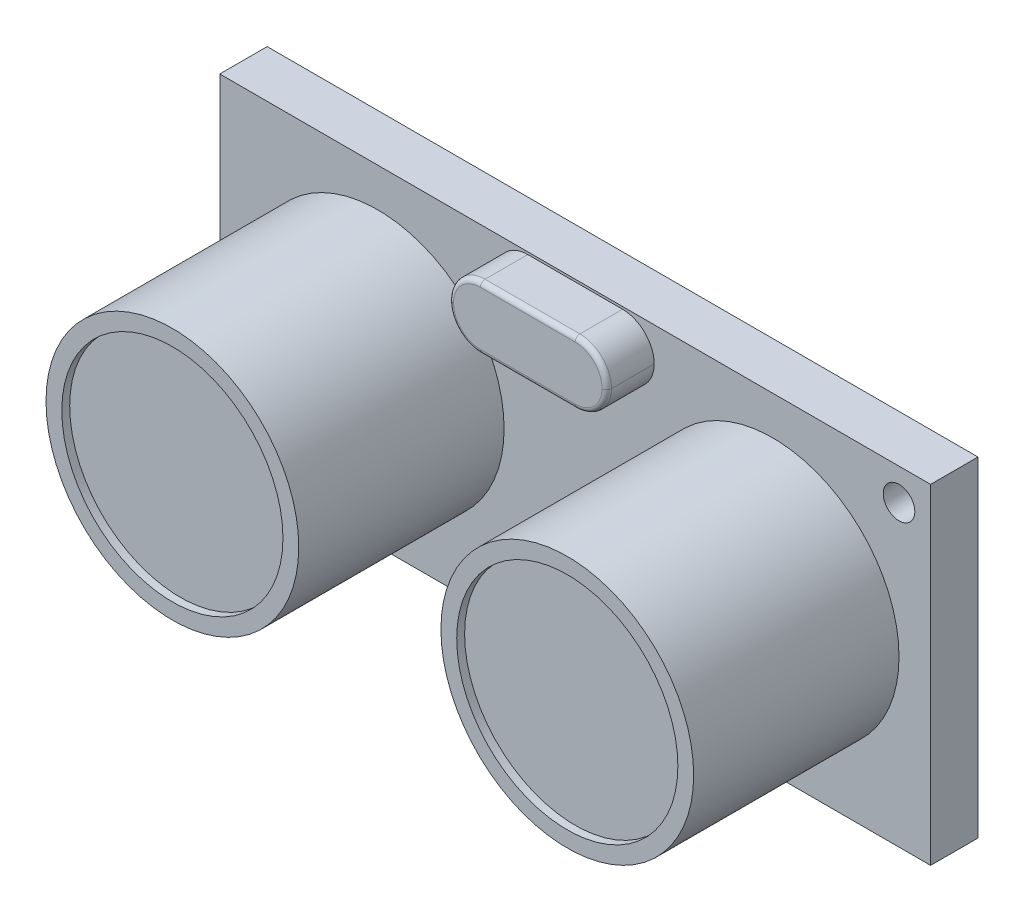
SolidWorks part; units mm, degrees
ref_plane "Front Plane" through (0, 0, 0) normal (0, 0, 1) x (1, 0, 0)
ref_plane "Top Plane" through (0, 0, 0) normal (0, 1, 0) x (1, 0, 0)
ref_plane "Right Plane" through (0, 0, 0) normal (1, 0, 0) x (0, 0, -1)
sketch "Sketch1" plane through (0, 0, 0) normal (0, 0, 1) x (1, 0, 0)
  line L0 (-22.5, 10.445) -> (22.5, 10.445)
  line L1 (-22.5, 10.445) -> (-22.5, -10.445)
  line L2 (-22.5, -10.445) -> (22.5, -10.445)
  line L3 (22.5, 10.445) -> (22.5, -10.445)
  line L4 (0, 10.445) -> (0, -10.445) construction
  line L5 (-22.5, 0) -> (22.5, 0) construction
  circle A2 centre (-20.5, -8.445) radius 1
  circle A3 centre (20.5, 8.445) radius 1
  point P16 (0, 0)
  point P26 (-22.5, 0)
  point P30 (22.5, 0)
  dimension "D16" = 2
  dimension "D4" = 2
  dimension "D2" = 2
  dimension "D3" = 2
  dimension "D5" = 2
  dimension "D12" = 45
  dimension "D13" = 20.89
other "AlignGroup1"
other "AlignGroup2"
other "AlignGroup3"
other "AlignGroup4"
other "AlignGroup5"
other "AlignGroup6"
extrude "Boss-Extrude1" add sketch "Sketch1" along normal blind 3
sketch "Sketch2" plane through (0, 0, 3) normal (0, 0, 1) x (1, 0, 0)
  line L1 (-22.5, -10.445) -> (22.5, -10.445) construction
  line L2 (0, -10.445) -> (0, 10.445) construction
  line L3 (22.5, 10.445) -> (-22.5, 10.445) construction
  circle A0 centre (-12.5, 0) radius 8
  circle A1 centre (12.5, 0) radius 8
  dimension "D1" = 25
  dimension "D3" = 16
  dimension "D2" = 12.5
extrude "Boss-Extrude2" add sketch "Sketch2" along normal blind 13
sketch "Sketch3" plane through (0, 0, 16) normal (0, 0, 1) x (1, 0, 0)
  circle A2 centre (-12.5, 0) radius 7
  circle A3 centre (-12.5, 0) radius 7
  circle A5 centre (12.5, 0) radius 7
  circle A6 centre (12.5, 0) radius 7
  dimension "D1" = 1
  dimension "D2" = 1
extrude "Cut-Extrude1" cut sketch "Sketch3" against normal blind 0.5
sketch "Sketch4" plane through (0, 0, 3) normal (0, 0, 1) x (1, 0, 0)
  line L3 (-22.5, 0) -> (22.5, 0) construction
  line L4 (-22.5, 10.445) -> (-22.5, -10.445) construction
  line L5 (22.5, -10.445) -> (22.5, 10.445) construction
  circle A5 centre (-5.08, -8.406) radius 0.5
  circle A6 centre (-2.54, -8.406) radius 0.5
  circle A7 centre (0, -8.406) radius 0.5
  circle A8 centre (2.54, -8.406) radius 0.5
  circle A9 centre (5.08, -8.406) radius 0.5
extrude "Extrude-Thin4" add sketch "Sketch4" along normal blind 0.1 and the other way blind 3.1 thin contours A5 | A6 | A7 | A8 | A9 thin type one direction wall 0.5
sketch "Sketch12" plane through (0, 0, 0) normal (0, 0, -1) x (-1, 0, 0)
  line L1 (20.0845, -7.493) -> (20.0845, 7.493) construction
  text T0 "SRF05" font "Arial Rounded MT Bold" height in points 8
sketch "Sketch13" plane through (0, 0, 3) normal (0, 0, 1) x (1, 0, 0)
  circle A0 centre (-5.08, -8.406) radius 0.5
  circle A1 centre (-2.54, -8.406) radius 0.5
  circle A2 centre (0, -8.406) radius 0.5
  circle A3 centre (2.54, -8.406) radius 0.5
  circle A4 centre (5.08, -8.406) radius 0.5
  dimension "D1" = 5
extrude "Cut-Extrude2" cut sketch "Sketch13" against normal through all
extrude "Boss-Extrude3" add sketch "Sketch12" along normal blind 0.1
sketch "Sketch15" plane through (0, 0, 3) normal (0, 0, 1) x (1, 0, 0)
  line L0 (22.5, 10.445) -> (-22.5, 10.445) construction
  line L5 (-5, 10.295) -> (5, 10.295)
  line L6 (-5, 10.295) -> (-5, 6.295)
  line L7 (-5, 6.295) -> (5, 6.295)
  line L8 (5, 10.295) -> (5, 6.295)
  line L9 (-5, 10.295) -> (5, 6.295) construction
  line L10 (-5, 6.295) -> (5, 10.295) construction
  point P0 (0, 8.295)
  dimension "D1" = 10
  dimension "D2" = 4
  dimension "D3" = 0.15
extrude "Boss-Extrude4" add sketch "Sketch15" along normal blind 3
fillet "Fillet1" radius 2 4 edges at (5, 10.295, 4.5) (5, 6.295, 4.5) (-5, 6.295, 4.5) (-5, 10.295, 4.5)
fillet "Fillet2" radius 0.3 6 edges at (0, 10.295, 6) (4.4142, 9.7092, 6) (4.4142, 6.8808, 6) (0, 6.295, 6) (-4.4142, 6.8808, 6) (-4.4142, 9.7092, 6)
